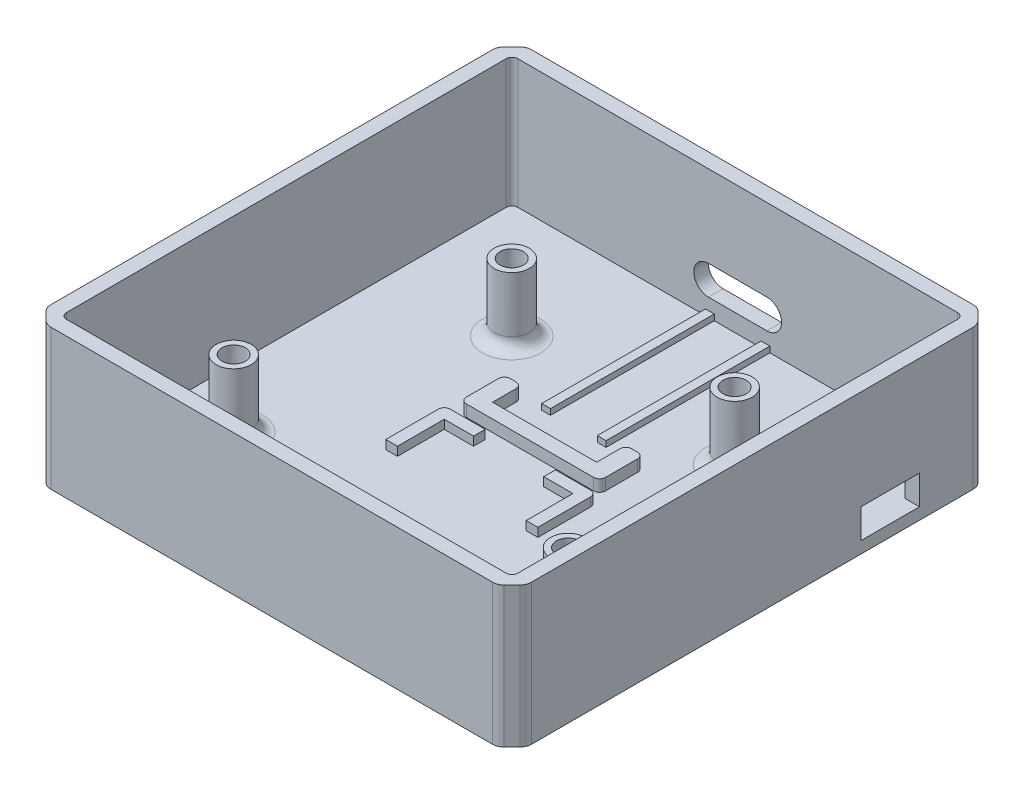
SolidWorks part; units mm, degrees
ref_plane "Front Plane" through (0, 0, 0) normal (0, 0, 1) x (1, 0, 0)
ref_plane "Top Plane" through (0, 0, 0) normal (0, 1, 0) x (1, 0, 0)
ref_plane "Right Plane" through (0, 0, 0) normal (1, 0, 0) x (0, 0, -1)
sketch "Sketch1" plane through (0, 0, 0) normal (0, 1, 0) x (1, 0, 0)
  line L1 (-38.575, -38.575) -> (38.575, -38.575)
  line L2 (-38.575, -38.575) -> (-38.575, 38.575)
  line L3 (-38.575, 38.575) -> (38.575, 38.575)
  line L4 (38.575, -38.575) -> (38.575, 38.575)
  line L5 (-38.575, -38.575) -> (38.575, 38.575) construction
  line L6 (-38.575, 38.575) -> (38.575, -38.575) construction
  point P0 (0, 0)
  dimension "D1" = 77.15
extrude "Boss-Extrude1" add sketch "Sketch1" along normal blind 2
sketch "Sketch2" plane through (0, 0, 0) normal (0, 1, 0) x (1, 0, 0)
  line L20 (38.575, -38.575) -> (38.575, 38.575) construction
  line L21 (38.575, 38.575) -> (-38.575, 38.575) construction
  line L22 (-38.575, 38.575) -> (-38.575, -38.575) construction
  line L23 (-38.575, -38.575) -> (38.575, -38.575) construction
  line L24 (41.075, -41.075) -> (41.075, 41.075)
  line L25 (41.075, 41.075) -> (-41.075, 41.075)
  line L26 (-41.075, 41.075) -> (-41.075, -41.075)
  line L27 (-41.075, -41.075) -> (41.075, -41.075)
  line L28 (41.075, -41.075) -> (41.075, 41.075)
  line L29 (41.075, 41.075) -> (-41.075, 41.075)
  line L30 (-41.075, 41.075) -> (-41.075, -41.075)
  line L31 (-41.075, -41.075) -> (41.075, -41.075)
  line L32 (38.575, -38.575) -> (38.575, 38.575)
  line L33 (38.575, 38.575) -> (-38.575, 38.575)
  line L34 (-38.575, 38.575) -> (-38.575, -38.575)
  line L35 (-38.575, -38.575) -> (38.575, -38.575)
  dimension "D1" = 2.5
extrude "Boss-Extrude2" add sketch "Sketch2" along normal blind 24
sketch "Sketch3" plane through (0, 2, 0) normal (0, 1, 0) x (1, 0, 0)
  line L0 (28.58, -19) -> (-28.58, -19) construction
  line L2 (19.05, 19) -> (-19.05, 19) construction
  circle A2 centre (-28.58, -19) radius 2
  circle A3 centre (28.58, -19) radius 2
  circle A4 centre (19.05, 19) radius 2
  circle A5 centre (-19.05, 19) radius 2
  circle A6 centre (-28.58, -19) radius 3
  circle A7 centre (-19.05, 19) radius 3
  circle A8 centre (28.58, -19) radius 3
  circle A9 centre (19.05, 19) radius 3
  point P0 (0, 0)
  point P2 (0, 19)
  point P17 (0, -19)
  dimension "D3" = 1
  dimension "D4" = 19
  dimension "D1" = 4
  dimension "D2" = 38.1
  dimension "D5" = 57.16
  dimension "D6" = 19
extrude "Boss-Extrude4" add sketch "Sketch3" along normal offset from surface (11.5 mm away) 10.5 up to face at (0, 24, 0)
sketch "Sketch11" plane through (0, 2, 0) normal (0, 1, 0) x (1, 0, 0)
  line L0 (-10, -31.575) -> (-10, -1.575)
  line L6 (-11, -32.575) -> (11, -32.575)
  line L7 (-11, -32.575) -> (-11, -0.575)
  line L8 (-11, -0.575) -> (11, -0.575)
  line L9 (11, -32.575) -> (11, -0.575)
  line L10 (-11, -32.575) -> (11, -0.575) construction
  line L11 (-11, -0.575) -> (11, -32.575) construction
  line L12 (38.575, 38.575) -> (-38.575, 38.575) construction
  line L13 (-8.89, 38.575) -> (8.89, 38.575) construction
  line L14 (-8.89, 38.575) -> (-8.89, 5.575) construction
  line L15 (-8.89, 5.575) -> (8.89, 5.575) construction
  line L16 (8.89, 38.575) -> (8.89, 5.575) construction
  line L17 (-8.89, 38.575) -> (8.89, 5.575) construction
  line L18 (-8.89, 5.575) -> (8.89, 38.575) construction
  line L27 (-10, -1.575) -> (10, -1.575)
  line L28 (10, -31.575) -> (10, -1.575)
  line L29 (-10, -31.575) -> (10, -31.575)
  line L30 (0, -13.2) -> (0, 13.2) construction
  line L31 (4, 38.575) -> (5.5, 38.575)
  line L32 (4, 38.575) -> (4, 10.575)
  line L33 (4, 10.575) -> (5.5, 10.575)
  line L34 (5.5, 38.575) -> (5.5, 10.575)
  line L35 (-4, 10.575) -> (-5.5, 10.575)
  line L36 (-5.5, 38.575) -> (-5.5, 10.575)
  line L37 (-4, 38.575) -> (-5.5, 38.575)
  line L38 (-4, 38.575) -> (-4, 10.575)
  line L39 (-38.575, -38.575) -> (38.575, -38.575) construction
  point P1 (0, 22.075)
  point P6 (0, -16.575)
  dimension "D1" = 33
  dimension "D2" = 17.78
  dimension "D3" = 1
  dimension "D4" = 20
  dimension "D5" = 6
  dimension "D6" = 30
  dimension "D7" = 4
  dimension "D8" = 1.5
  dimension "D9" = 5
extrude "Boss-Extrude7" add sketch "Sketch11" along normal blind 1 contours L35 L36 L37 L38 | L32 L31 L34 L33
sketch "Sketch17" plane through (0, 2, 0) normal (0, 1, 0) x (1, 0, 0)
  line L0 (-8.89, 10.575) -> (-8.89, 5.575)
  line L1 (-8.89, 38.575) -> (-8.89, 5.575) construction
  line L2 (-8.89, 5.575) -> (8.89, 5.575)
  line L3 (8.89, 5.575) -> (8.89, 10.575)
  line L4 (8.89, 38.575) -> (8.89, 5.575) construction
  line L5 (8.89, 10.575) -> (11.89, 10.575)
  line L6 (11.89, 10.575) -> (11.89, 3.075)
  line L7 (11.89, 3.075) -> (-11.89, 3.075)
  line L8 (-11.89, 3.075) -> (-11.89, 10.575)
  line L9 (-11.89, 10.575) -> (-8.89, 10.575)
  dimension "D1" = 3
  dimension "D2" = 2.5
  dimension "D3" = 5
extrude "Boss-Extrude8" add sketch "Sketch17" along normal blind 2
sketch "Sketch4" plane through (0, 0, 0) normal (1, 0, 0) x (0, 0, -1)
  line L0 (0, 0) -> (0, 24) construction
  line L1 (-41.075, 24) -> (41.075, 24) construction
sketch "Sketch7" plane through (0, 0, 0) normal (0, -1, 0) x (1, 0, 0)
  line L0 (41.075, -41.075) -> (-41.075, -41.075) construction
  line L1 (-41.075, -41.075) -> (-41.075, 41.075) construction
  line L2 (0, 0) -> (-25.075, -25.075) construction
  circle A0 centre (-25.075, -25.075) radius 4
  circle A1 centre (-25.075, 25.075) radius 4
  circle A2 centre (25.075, 25.075) radius 4
  circle A3 centre (25.075, -25.075) radius 4
  dimension "D1" = 8
  dimension "D4" = 4
extrude "Cut-Extrude1" cut sketch "Sketch7" against normal offset from surface (1 mm away) 1 up to face at (0, 2, -16.3833)
sketch "Sketch10" plane through (0, 0, -38.575) normal (0, 0, -1) x (-1, 0, 0)
  line L0 (-5, 7.5) -> (5, 7.5) construction
  line L1 (-5, 10) -> (5, 10)
  line L2 (-5, 5) -> (5, 5)
  line L3 (-38.575, 2) -> (-5.5, 2) construction
  line L4 (-38.575, 2) -> (-5.5, 2) construction
  arc A1 (-5, 10) -> (-5, 5) centre (-5, 7.5) ccw
  arc A2 (5, 5) -> (5, 10) centre (5, 7.5) ccw
  point P2 (0, 7.5)
  dimension "D1" = 10
  dimension "D2" = 5
  dimension "D3" = 4.5
extrude "Cut-Extrude2" cut sketch "Sketch10" along normal up to surface (2.5 mm away) up to face at (0, 12, -41.075)
sketch "Sketch16" plane through (38.575, 0, 0) normal (-1, 0, 0) x (0, 0, 1)
  line L0 (38.575, 2) -> (-38.575, 2) construction
  line L1 (-28.575, 2) -> (-18.575, 2)
  line L2 (-28.575, 2) -> (-28.575, 7)
  line L3 (-28.575, 7) -> (-18.575, 7)
  line L4 (-18.575, 2) -> (-18.575, 7)
  dimension "D1" = 10
  dimension "D2" = 5
  dimension "D3" = 10
extrude "Cut-Extrude3" cut sketch "Sketch16" against normal up to surface (2.5 mm away) up to face at (41.075, 12, 0)
sketch "Sketch15" plane through (0, 2, 0) normal (0, 1, 0) x (1, 0, 0)
  line L0 (-11, -0.575) -> (-11, -8.575)
  line L1 (-11, -32.575) -> (-11, -0.575) construction
  line L2 (-11, -8.575) -> (-13, -8.575)
  line L3 (-13, -8.575) -> (-13, 1.425)
  line L4 (-13, 1.425) -> (-6, 1.425)
  line L5 (-6, 1.425) -> (-6, -0.575)
  line L6 (-11, -0.575) -> (11, -0.575) construction
  line L7 (-6, -0.575) -> (-11, -0.575)
  line L8 (-13, -24.575) -> (-11, -24.575)
  line L9 (-11, -24.575) -> (-11, -32.575)
  line L10 (-11, -32.575) -> (-6, -32.575)
  line L11 (-11, -32.575) -> (11, -32.575) construction
  line L12 (-6, -32.575) -> (-6, -34.575)
  line L13 (-6, -34.575) -> (-13, -34.575)
  line L14 (-13, -24.575) -> (-13, -34.575)
  line L15 (0, -13.2) -> (0, 13.2) construction
  line L16 (13, -24.575) -> (11, -24.575)
  line L17 (11, -24.575) -> (11, -32.575)
  line L18 (11, -32.575) -> (6, -32.575)
  line L19 (6, -32.575) -> (6, -34.575)
  line L20 (6, -34.575) -> (13, -34.575)
  line L21 (13, -24.575) -> (13, -34.575)
  line L22 (6, 1.425) -> (6, -0.575)
  line L23 (13, 1.425) -> (6, 1.425)
  line L24 (13, -8.575) -> (13, 1.425)
  line L25 (11, -8.575) -> (13, -8.575)
  line L26 (11, -0.575) -> (11, -8.575)
  line L27 (6, -0.575) -> (11, -0.575)
  dimension "D1" = 7
  dimension "D2" = 10
  dimension "D4" = 2
extrude "Boss-Extrude6" add sketch "Sketch15" along normal blind 1.5 contours L7 L0 L2 L3 L4 L5 | L22 L27 L26 L25 L24 L23 | L14 L13 L12 L10 L9 L8 | L16 L17 L18 L19 L20 L21
fillet "Fillet1" radius 2 4 edges at (28.58, 2, 16) (19.05, 2, -22) (-28.58, 2, 16) (-19.05, 2, -22)
fillet "Fillet2" radius 1 10 edges at (-13, 2.75, 34.575) (13, 2.75, 34.575) (13, 2.75, -1.425) (-13, 2.75, -1.425) (-11.89, 3, -10.575) (11.89, 3, -10.575) (11.89, 3, -3.075) (-11.89, 3, -3.075) (8.89, 3, -10.575) (-8.89, 3, -10.575)
chamfer "Chamfer1" distance 2.5 angle 45 4 edges at (41.075, 12, -41.075) (-41.075, 12, 41.075) (41.075, 12, 41.075) (-41.075, 12, -41.075)
fillet "Fillet3" radius 2 8 edges at (-41.075, 12, -38.575) (-38.575, 12, -41.075) (38.575, 12, -41.075) (41.075, 12, -38.575) (41.075, 12, 38.575) (38.575, 12, 41.075) (-38.575, 12, 41.075) (-41.075, 12, 38.575) tangent propagation no
fillet "Fillet4" radius 1 4 edges at (38.575, 13, -38.575) (-38.575, 13, -38.575) (-38.575, 13, 38.575) (38.575, 13, 38.575)
